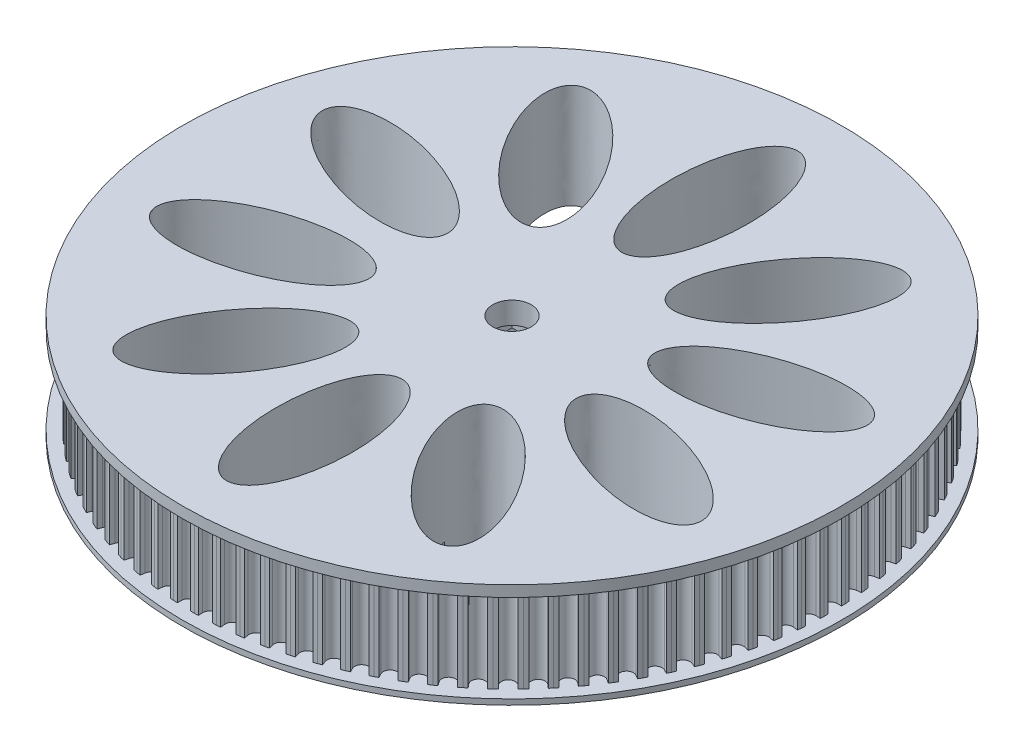
SolidWorks part; units mm, degrees
ref_plane "Front Plane" through (0, 0, 0) normal (0, 0, 1) x (1, 0, 0)
ref_plane "Top Plane" through (0, 0, 0) normal (0, 1, 0) x (1, 0, 0)
ref_plane "Right Plane" through (0, 0, 0) normal (1, 0, 0) x (0, 0, -1)
sketch "Sketch1" plane through (0, 0, 0) normal (0, 1, 0) x (1, 0, 0)
  circle A0 centre (0, 0) radius 30
  circle A1 centre (0, 0) radius 8.55
  ellipse E0 centre (0, 18) end of major axis (0, 26) minor radius 3.5
  ellipse E1 centre (10.5801, 14.5623) end of major axis (15.2824, 21.0344) minor radius 3.5
  ellipse E2 centre (17.119, 5.5623) end of major axis (24.7275, 8.0344) minor radius 3.5
  ellipse E3 centre (17.119, -5.5623) end of major axis (24.7275, -8.0344) minor radius 3.5
  ellipse E4 centre (10.5801, -14.5623) end of major axis (15.2824, -21.0344) minor radius 3.5
  ellipse E5 centre (0, -18) end of major axis (0, -26) minor radius 3.5
  ellipse E6 centre (-10.5801, -14.5623) end of major axis (-15.2824, -21.0344) minor radius 3.5
  ellipse E7 centre (-17.119, -5.5623) end of major axis (-24.7275, -8.0344) minor radius 3.5
  ellipse E8 centre (-17.119, 5.5623) end of major axis (-24.7275, 8.0344) minor radius 3.5
  ellipse E9 centre (-10.5801, 14.5623) end of major axis (-5.8779, 8.0902) minor radius 3.5
  point P66 (0, 0)
  dimension "D1" = 60
  dimension "D2" = 17.1
  dimension "D3" = 18
  dimension "D4" = 7
  dimension "D5" = 16
  dimension "D6" = 10
extrude "Boss-Extrude1" add sketch "Sketch1" along normal blind 11.5
sketch "Sketch2" plane through (0, 11.5, 0) normal (0, 1, 0) x (1, 0, 0)
  circle A0 centre (0, 0) radius 8.55
  circle A1 centre (0, 0) radius 8.55 construction
  circle A2 centre (0, 0) radius 1.75
  dimension "D1" = 3.5
extrude "Boss-Extrude2" add sketch "Sketch2" against normal blind 2
sketch "Sketch3" plane through (0, 9.5, 0) normal (0, -1, 0) x (-1, 0, 0)
  line L1 (6.0458, 6.0458) -> (-6.0458, 6.0458)
  line L2 (6.0458, 6.0458) -> (6.0458, -6.0458)
  line L3 (6.0458, -6.0458) -> (-6.0458, -6.0458)
  line L4 (-6.0458, 6.0458) -> (-6.0458, -6.0458)
  line L5 (6.0458, 6.0458) -> (-6.0458, -6.0458) construction
  line L6 (6.0458, -6.0458) -> (-6.0458, 6.0458) construction
  circle A0 centre (0, 0) radius 8.55 construction
  circle A1 centre (0, 0) radius 8.55 construction
  circle A2 centre (0, 0) radius 8.55
  point P0 (0, 0)
  circle M6 centre (0, 0) radius 8.55
extrude "Boss-Extrude3" add sketch "Sketch3" along normal blind 5 contours L3 M6 | L2 M6 | L4 M6 | L1 M6 region at (-7.0612, 9.5, 0) region at (0, 9.5, -7.0612) region at (7.0612, 9.5, 0) region at (0, 9.5, 7.0612)
sketch "Sketch4" plane through (0, 0, 0) normal (0, -1, 0) x (-1, 0, 0)
  circle A0 centre (0, 0) radius 12.55
  circle A1 centre (0, 0) radius 30
  circle A2 centre (0, 0) radius 30 construction
  arc A3 (-6.0458, 6.0458) -> (-6.0458, -6.0458) centre (0, 0) ccw construction
  dimension "D1" = 4
extrude "Cut-Extrude1" cut sketch "Sketch4" against normal blind 2 contours A1 | A0
sketch "Sketch5" plane through (0, 11.5, 0) normal (0, 1, 0) x (1, 0, 0)
  line L0 (0.63, 28.9) -> (2, 28.9)
  line L1 (-2, 28.9) -> (-0.63, 28.9)
  line L2 (-2, 28.9) -> (-2, 31.9)
  line L3 (-2, 31.9) -> (2, 31.9)
  line L4 (2, 28.9) -> (2, 31.9)
  line L5 (-0.63, 28.5) -> (-0.63, 28.9)
  line L6 (0.63, 28.5) -> (0.63, 28.9)
  arc A1 (-0.63, 28.5) -> (0.63, 28.5) centre (0, 28.5) ccw
  point P12 (0, 31.9)
  circle M9 centre (0, 0) radius 30
  dimension "D1" = 28.5
  dimension "D4" = 0.4
  dimension "D5" = 3
  dimension "D2" = 1.26
  dimension "D3" = 4
extrude "Cut-Extrude2" cut sketch "Sketch5" against normal blind 8 from offset 1 contours L5 A1 L6 L0 L4 L2 L1 M9 | L4 L3 L2 M9 region at (0, 11.5, -29.2323) region at (0, 11.5, -30.9388) offset against normal yes
pattern_circular "CirPattern1" count 93 over 360 about axis through (0, 9.5, 0) along (0, 1, 0) of "Cut-Extrude2" reverse direction yes
